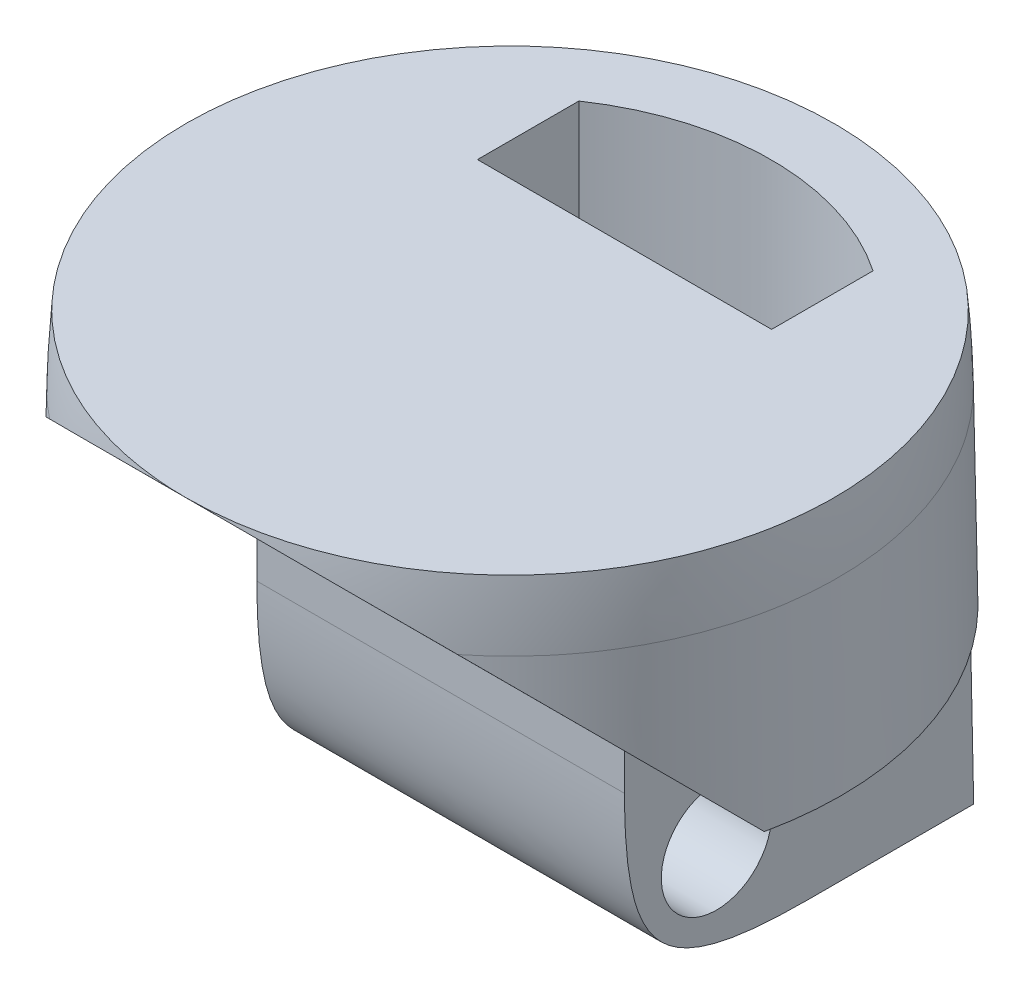
SolidWorks part; units mm, degrees
ref_plane "Front Plane" through (0, 0, 0) normal (0, 0, 1) x (1, 0, 0)
ref_plane "Top Plane" through (0, 0, 0) normal (0, 1, 0) x (1, 0, 0)
ref_plane "Right Plane" through (0, 0, 0) normal (1, 0, 0) x (0, 0, -1)
sketch "Sketch1" plane through (0, 0, 0) normal (0, 1, 0) x (1, 0, 0)
  circle A0 centre (0, 0) radius 9
  dimension "D1" = 18
extrude "Boss-Extrude1" add sketch "Sketch1" along normal blind 15 draft 1 and the other way blind 6 draft 1
sketch "Sketch3" plane through (0, 0, 0) normal (1, 0, 0) x (0, 0, -1)
  line L0 (-1.8929, -0.1305) -> (-1.8929, -6.1305) construction
  line L1 (-1.8861, -6) -> (-1.8861, 0)
  line L2 (-9.1047, -6) -> (9.1047, -6) construction
  line L3 (-1.8861, 0) -> (-9.9298, 8.0437)
  line L4 (-9.9298, 8.0437) -> (-9.9298, -6)
  line L5 (-9.9298, -6) -> (-1.8861, -6)
  dimension "D1" = 6
  dimension "D2" = 135
  dimension "D3" = 6
extrude "Cut-Extrude1" cut sketch "Sketch3" against normal through all both and the other way through all
sketch "Sketch4" plane through (0, 0, 1.8861) normal (0, 0, 1) x (1, 0, 0)
  line L0 (8.9072, -6) -> (-8.9072, -6) construction
  line L1 (-5, -6) -> (5, -6)
  line L2 (-5, -6) -> (-5, 0)
  line L3 (-5, 0) -> (5, 0)
  line L4 (5, -6) -> (5, 0)
  line L5 (-5, -6) -> (5, 0) construction
  line L6 (-5, 0) -> (5, -6) construction
  line L8 (-11.5027, -6) -> (11.5027, -6)
  line L9 (-11.5027, -6) -> (-11.5027, 0)
  line L10 (-11.5027, 0) -> (11.5027, 0)
  line L11 (11.5027, -6) -> (11.5027, 0)
  line L12 (-11.5027, -6) -> (11.5027, 0) construction
  line L13 (-11.5027, 0) -> (11.5027, -6) construction
  point P0 (0, -3)
  point P9 (0, -3)
  dimension "D1" = 6
  dimension "D2" = 10
extrude "Cut-Extrude2" cut sketch "Sketch4" against normal through all
sketch "Sketch5" plane through (5, 0, 0) normal (1, 0, 0) x (0, 0, -1)
  line L0 (7.6089, -6) -> (-1.8861, -6) construction
  line L1 (-1.8861, -6) -> (-1.8861, 0) construction
  circle A0 centre (0.6139, -3.5) radius 1.5
  dimension "D3" = 3
  dimension "D1" = 2.5
  dimension "D2" = 2.5
extrude "Cut-Extrude3" cut sketch "Sketch5" against normal through all
fillet "Fillet1" radius 5 1 edges at (0, -6, 1.8861)
fillet "Fillet2" radius 10 1 edges at (0, 15, 8.7382)
sketch "Sketch6" plane through (0, 0, 0) normal (1, 0, 0) x (0, 0, -1)
  line L1 (-8.8136, 6.9275) -> (11.2542, 6.9275)
  line L2 (-8.8136, 6.9275) -> (-8.8136, 15.6528)
  line L3 (-8.8136, 15.6528) -> (11.2542, 15.6528)
  line L4 (11.2542, 6.9275) -> (11.2542, 15.6528)
  point P5 (11.2542, 15.6528)
extrude "Cut-Extrude4" cut sketch "Sketch6" against normal through all both and the other way through all
sketch "Sketch7" plane through (0, -6, 0) normal (0, -1, 0) x (1, 0, 0)
  line L6 (4, -3.1139) -> (4, -5.8717)
  line L7 (5, -3.1139) -> (-5, -3.1139) construction
  line L8 (4, -3.1139) -> (-4, -3.1139)
  line L9 (-4, -3.1139) -> (-4, -5.8717)
  line L11 (-5, -7.6089) -> (-5, -3.1139) construction
  line L12 (5, -7.6089) -> (5, -3.1139) construction
  arc A6 (-3.9017, -5.9375) -> (3.9017, -5.9375) centre (0, 0) ccw
  arc A7 (-4, -5.8717) -> (4, -5.8717) centre (0, 0) ccw
  dimension "D2" = 1
  dimension "D3" = 1
  dimension "D1" = 2
extrude "Cut-Extrude5" cut sketch "Sketch7" against normal through all
